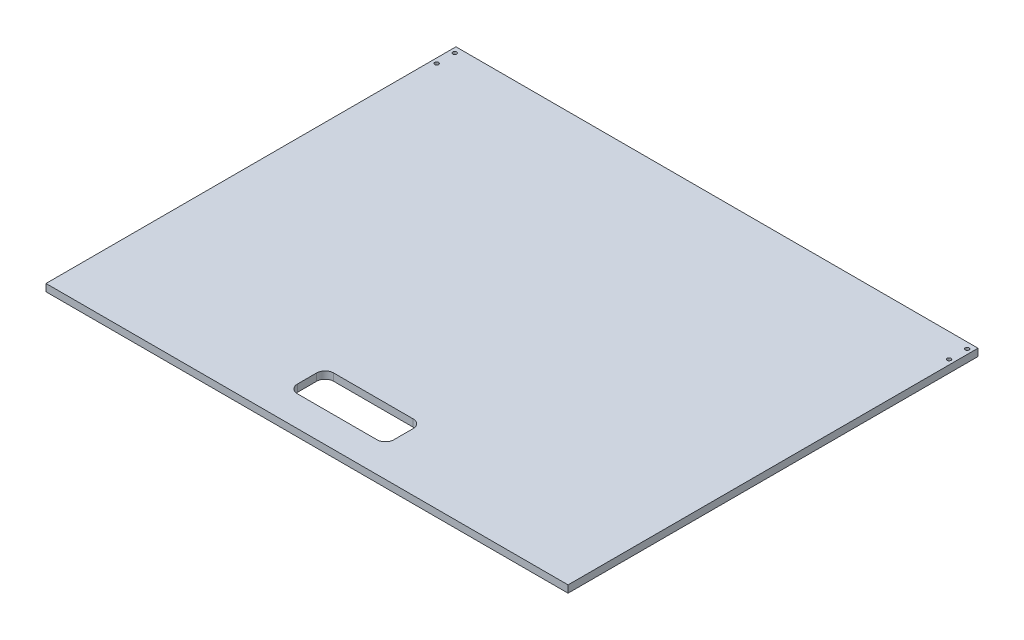
SolidWorks part; units mm, degrees
ref_plane "Front Plane" through (0, 0, 0) normal (0, 0, 1) x (1, 0, 0)
ref_plane "Top Plane" through (0, 0, 0) normal (0, 1, 0) x (1, 0, 0)
ref_plane "Right Plane" through (0, 0, 0) normal (1, 0, 0) x (0, 0, -1)
sketch "Sketch1" plane through (0, 0, 0) normal (0, 1, 0) x (1, 0, 0)
  line L1 (-216.5, -170) -> (216.5, -170)
  line L2 (-216.5, -170) -> (-216.5, 170)
  line L3 (-216.5, 170) -> (216.5, 170)
  line L4 (216.5, -170) -> (216.5, 170)
  line L5 (-216.5, -170) -> (216.5, 170) construction
  line L6 (-216.5, 170) -> (216.5, -170) construction
  point P0 (0, 0)
  point P6 (216.5, 177)
  dimension "D1" = 433
  dimension "D2" = 340
extrude "Boss-Extrude1" add sketch "Sketch1" along normal blind 6
sketch "Sketch2" plane through (0, 0, 0) normal (0, -1, 0) x (1, 0, 0)
  line L0 (216.5, -170) -> (-216.5, -170) construction
  line L1 (216.5, 170) -> (216.5, -170) construction
  circle A0 centre (212.5, -150) radius 1.6
  circle A1 centre (212.5, -165) radius 1.6
  point P6 (0, 0)
  point P7 (202.4909, -156)
  dimension "D1" = 5
  dimension "D3" = 3.2
  dimension "D2" = 15
  dimension "D4" = 4
extrude "Cut-Extrude1" cut sketch "Sketch2" against normal through all
mirror "Mirror1" about plane through (0, 0, 0) normal (1, 0, 0) of "Cut-Extrude1"
sketch "Sketch3" plane through (0, 6, 0) normal (0, 1, 0) x (1, 0, 0)
  line L0 (-216.5, -170) -> (216.5, -170) construction
  line L1 (-33, -145) -> (33, -145)
  line L2 (-40, -138) -> (-40, -122)
  line L3 (-33, -115) -> (33, -115)
  line L4 (40, -138) -> (40, -122)
  line L5 (-40, -145) -> (40, -115) construction
  line L6 (-40, -115) -> (40, -145) construction
  arc A0 (-40, -122) -> (-33, -115) centre (-33, -122) cw
  arc A1 (-33, -145) -> (-40, -138) centre (-33, -138) cw
  arc A2 (33, -145) -> (40, -138) centre (33, -138) ccw
  arc A3 (33, -115) -> (40, -122) centre (33, -122) cw
  point P0 (0, -130)
  point P7 (0, 0)
  dimension "D4" = 7
  dimension "D1" = 25
  dimension "D2" = 80
  dimension "D3" = 30
extrude "Cut-Extrude2" cut sketch "Sketch3" against normal through all
